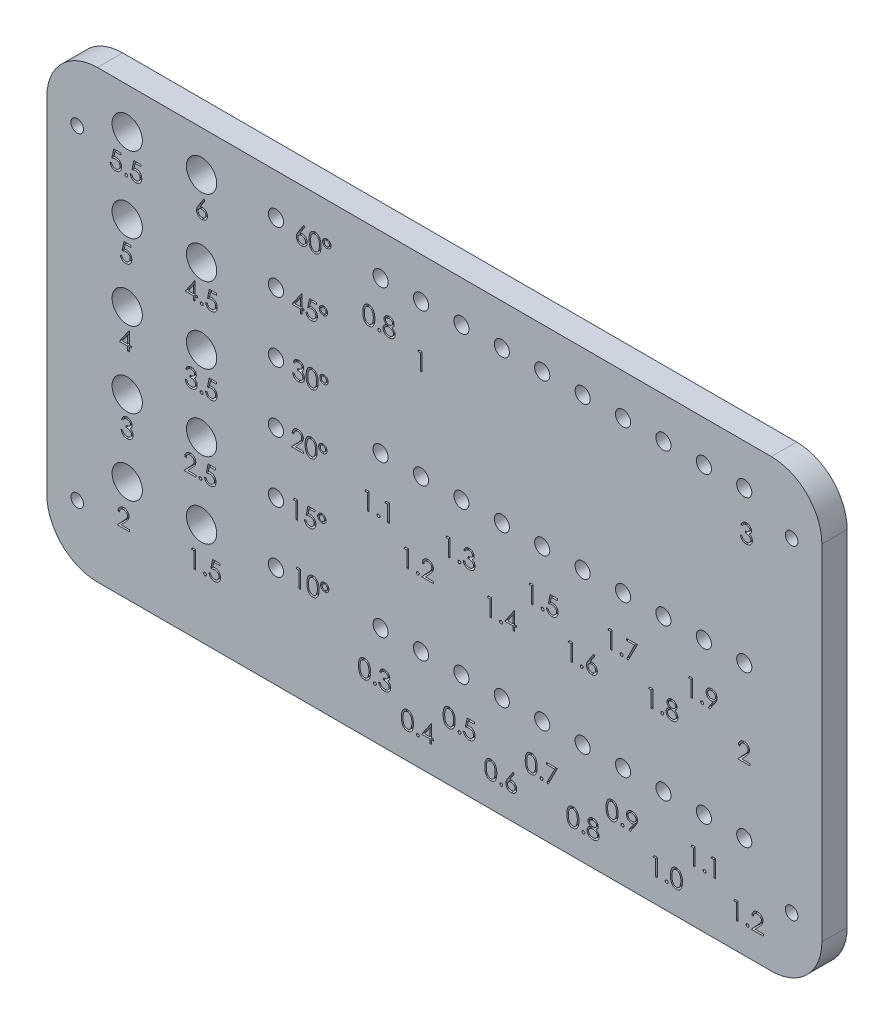
SolidWorks part; units mm, degrees
ref_plane "Front Plane" through (0, 0, 0) normal (0, 0, 1) x (1, 0, 0)
ref_plane "Top Plane" through (0, 0, 0) normal (0, 1, 0) x (1, 0, 0)
ref_plane "Right Plane" through (0, 0, 0) normal (1, 0, 0) x (0, 0, -1)
sketch "Sketch1" plane through (0, 0, 0) normal (0, 0, 1) x (1, 0, 0)
  line L0 (0, 0) -> (0, 52.8809) construction
  line L1 (0, 0) -> (35.6862, 0) construction
  line L2 (0, 15) -> (39.9349, 15) construction
  line L3 (0, -15) -> (39.9349, -15) construction
  line L4 (-71.4458, 30) -> (-71.4458, -30) construction
  line L5 (-56.7239, 30) -> (-56.7239, -30) construction
  line L6 (36, 30) -> (0, 30) construction
  line L7 (-86.1678, 30) -> (-86.1678, -30) construction
  line L8 (-96.0772, 26.0928) -> (-96.0772, -38.1331) construction
  line L9 (-102.0772, -50.1331) -> (51.3707, -50.1331)
  line L10 (-102.0772, -50.1331) -> (-102.0772, 38.0928)
  line L11 (-102.0772, 38.0928) -> (51.3707, 38.0928)
  line L12 (51.3707, -50.1331) -> (51.3707, 38.0928)
  line L13 (-96.0772, -38.1331) -> (45.3707, -38.1331) construction
  line L14 (45.3707, -38.1331) -> (45.3707, 26.0928) construction
  line L15 (45.3707, 26.0928) -> (-96.0772, 26.0928) construction
  circle A0 centre (4, 0) radius 1.5
  circle A1 centre (12, 0) radius 1.5
  circle A2 centre (20, 0) radius 1.5
  circle A3 centre (28, 0) radius 1.5
  circle A4 centre (36, 0) radius 1.5
  circle A5 centre (-36, 0) radius 1.5
  circle A6 centre (-28, 0) radius 1.5
  circle A7 centre (-20, 0) radius 1.5
  circle A8 centre (-12, 0) radius 1.5
  circle A9 centre (-4, 0) radius 1.5
  circle A10 centre (-4, -30) radius 1.5
  circle A11 centre (-12, -30) radius 1.5
  circle A12 centre (-20, -30) radius 1.5
  circle A13 centre (-28, -30) radius 1.5
  circle A14 centre (-36, -30) radius 1.5
  circle A15 centre (36, -30) radius 1.5
  circle A16 centre (28, -30) radius 1.5
  circle A17 centre (20, -30) radius 1.5
  circle A18 centre (12, -30) radius 1.5
  circle A19 centre (4, -30) radius 1.5
  circle A20 centre (-4, 30) radius 1.5
  circle A21 centre (-12, 30) radius 1.5
  circle A22 centre (-20, 30) radius 1.5
  circle A23 centre (-28, 30) radius 1.5
  circle A24 centre (-36, 30) radius 1.5
  circle A25 centre (36, 30) radius 1.5
  circle A26 centre (28, 30) radius 1.5
  circle A27 centre (20, 30) radius 1.5
  circle A28 centre (12, 30) radius 1.5
  circle A29 centre (4, 30) radius 1.5
  circle A30 centre (-86.1678, -30) radius 3
  circle A31 centre (-71.4458, -30) radius 3
  circle A32 centre (-71.4458, 0) radius 3
  circle A33 centre (-71.4458, -15) radius 3
  circle A34 centre (-86.1678, -15) radius 3
  circle A35 centre (-86.1678, 0) radius 3
  circle A36 centre (-86.1678, 15) radius 3
  circle A37 centre (-71.4458, 15) radius 3
  circle A38 centre (-86.1678, 30) radius 3
  circle A39 centre (-71.4458, 30) radius 3
  circle A45 centre (-56.7239, 30) radius 1.5
  circle A46 centre (-56.7239, 18) radius 1.5
  circle A48 centre (-56.7239, -18) radius 1.5
  circle A49 centre (-56.7239, -30) radius 1.5
  circle A50 centre (-56.7239, -6) radius 1.5
  circle A51 centre (-56.7239, 6) radius 1.5
  circle A52 centre (-96.0772, 26.0928) radius 1.25
  circle A53 centre (-96.0772, -38.1331) radius 1.25
  circle A54 centre (45.3707, 26.0928) radius 1.25
  circle A55 centre (45.3707, -38.1331) radius 1.25
  text T0 "0.8"
  text T1 "1"
  text T2 "3"
  text T3 "1.5\r\n"
  text T4 "2"
  text T5 "2.5"
  text T6 "3"
  text T7 "4"
  text T8 "4.5"
  text T9 "5"
  text T10 "3.5"
  text T11 "5.5"
  text T12 "6"
  text T13 "1.1"
  text T14 "1.2"
  text T15 "1.3"
  text T16 "1.4"
  text T17 "1.5"
  text T18 "1.6"
  text T19 "1.7"
  text T20 "1.8"
  text T21 "1.9"
  text T22 "2"
  text T23 "0.3"
  text T24 "0.4"
  text T25 "0.5"
  text T26 "0.6"
  text T27 "0.7"
  text T28 "0.8"
  text T29 "0.9"
  text T30 "1.0"
  text T31 "1.1"
  text T32 "1.2"
  text T33 "10°"
  text T34 "60°"
  text T35 "45°\r\n"
  text T36 "30°"
  text T37 "20°"
  text T38 "15°"
  dimension "D1" = 3
  dimension "D8" = 6
  dimension "D9" = 6
  dimension "D15" = 6
  dimension "D16" = 2.5
  dimension "D2" = 8
  dimension "D3" = 4
  dimension "D4" = 8
  dimension "D5" = 8
  dimension "D6" = 8
  dimension "D7" = 15
  dimension "D10" = 12
  dimension "D11" = 12
  dimension "D12" = 12
  dimension "D13" = 12
  dimension "D14" = 12
  dimension "D17" = 12
  dimension "D18" = 12
extrude "Boss-Extrude1" add sketch "Sketch1" along normal blind 5
fillet "Fillet1" radius 10 4 edges at (51.3707, -50.1331, 2.5) (51.3707, 38.0928, 2.5) (-102.0772, -50.1331, 2.5) (-102.0772, 38.0928, 2.5)
